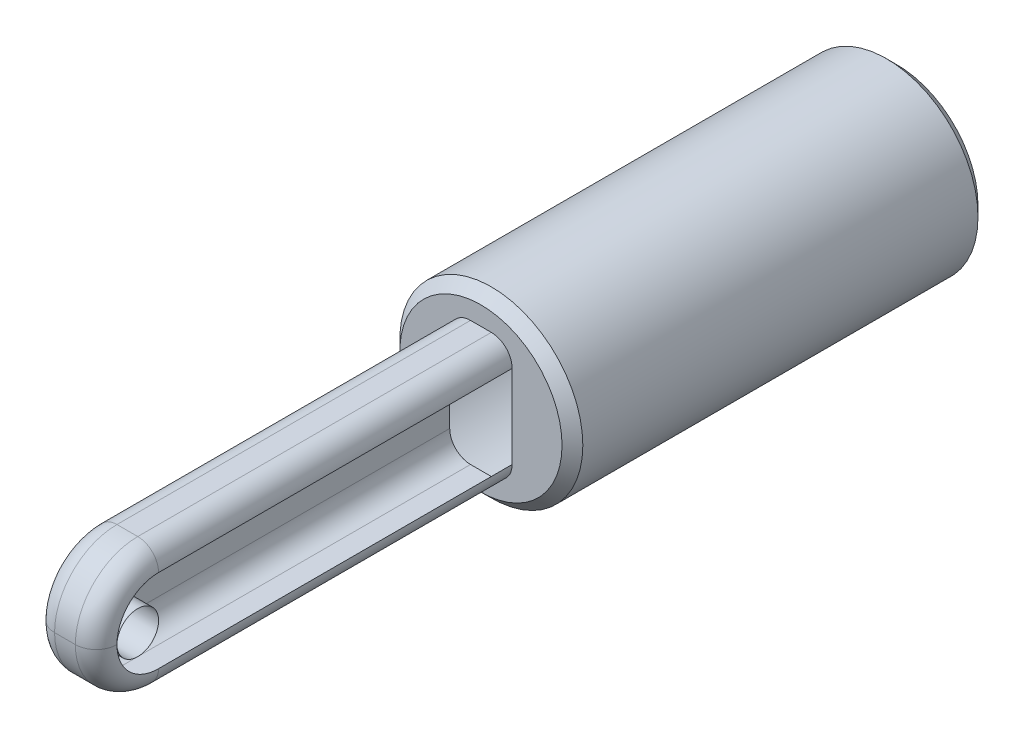
SolidWorks part; units mm, degrees
ref_plane "Front" through (0, 0, 0) normal (0, 0, 1) x (1, 0, 0)
ref_plane "Top" through (0, 0, 0) normal (0, 1, 0) x (1, 0, 0)
ref_plane "Right" through (0, 0, 0) normal (1, 0, 0) x (0, 0, -1)
sketch "Sketch2" plane through (0, 0, 0) normal (0, 0, 1) x (1, 0, 0)
  circle A0 centre (0, 0) radius 22
  dimension "D1" = 44
extrude "Boss-Extrude1" add sketch "Sketch2" against normal blind 100
sketch "Sketch4" plane through (0, 0, 0) normal (1, 0, 0) x (0, 0, -1)
  line L0 (0, 22) -> (0, -22) construction
  line L1 (0, 15) -> (-100, 15)
  line L2 (0, 15) -> (0, -15)
  line L3 (0, -15) -> (-100, -15)
  line L4 (-100, 15) -> (-100, -15)
  point P6 (0, 0)
  dimension "D1" = 30
  dimension "D2" = 100
extrude "Boss-Extrude2" add sketch "Sketch4" along normal mid plane 15
fillet "Fillet1" radius 15 2 edges at (0, -15, 100) (0, 15, 100)
sketch "Sketch5" plane through (7.5, 0, 0) normal (1, 0, 0) x (0, 0, -1)
  circle A0 centre (-90, 0) radius 5
  dimension "D1" = 10
  dimension "D2" = 90
extrude "Cut-Extrude1" cut sketch "Sketch5" against normal through all
fillet "Fillet2" radius 5 8 edges at (-7.5, -15, 42.5) (-7.5, -10.6066, 95.6066) (-7.5, 10.6066, 95.6066) (7.5, -15, 42.5) (7.5, -10.6066, 95.6066) (7.5, 10.6066, 95.6066) (-7.5, 15, 42.5) (7.5, 15, 42.5)
chamfer "Chamfer1" distance 2.5 angle 45 2 edges at (22, 0, -100) (22, 0, 0)
